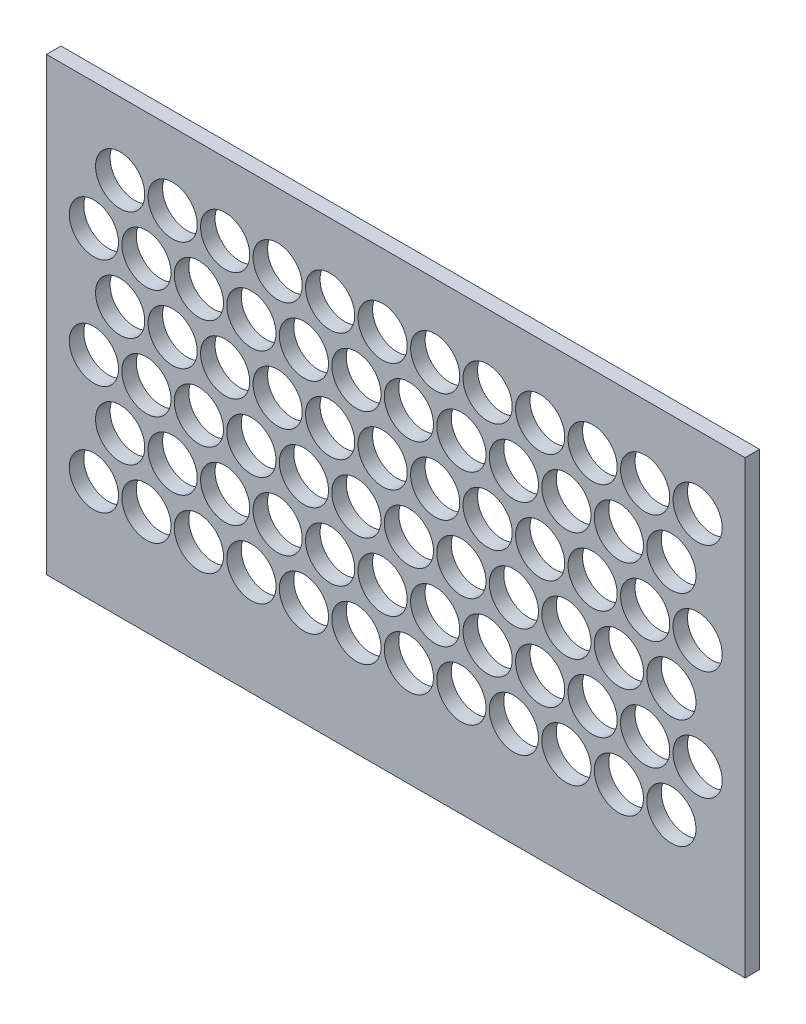
SolidWorks part; units mm, degrees
material "ABS"
ref_plane "X-Y Datum" through (0, 0, 0) normal (0, 0, 1) x (1, 0, 0)
ref_plane "X-Z Datum" through (0, 0, 0) normal (0, 1, 0) x (1, 0, 0)
ref_plane "Y-Z Datum" through (0, 0, 0) normal (1, 0, 0) x (0, 0, -1)
sketch "Sketch1" plane through (0, 0, 0) normal (0, 0, 1) x (1, 0, 0)
  line L1 (-143.025, 70.775) -> (143.025, 70.775)
  line L2 (-143.025, 70.775) -> (-143.025, -70.775)
  line L3 (-143.025, -70.775) -> (143.025, -70.775)
  line L4 (143.025, 70.775) -> (143.025, -70.775)
  line L5 (-143.025, 70.775) -> (143.025, -70.775) construction
  line L6 (-143.025, -70.775) -> (143.025, 70.775) construction
  line L13 (-153.025, -105.775) -> (153.025, -105.775)
  line L14 (-153.025, 91.65) -> (153.025, 91.65)
  line L15 (-153.025, 91.65) -> (-153.025, -105.775)
  line L16 (153.025, 91.65) -> (153.025, -105.775)
  line L17 (153.025, 70.775) -> (153.025, -70.775) construction
  line L18 (-143.025, 91.65) -> (143.025, 91.65) construction
  line L19 (-143.025, -105.775) -> (143.025, -105.775) construction
  line L20 (-153.025, 70.775) -> (-153.025, -70.775) construction
  line L21 (-132.25, -60) -> (-109.25, -60) construction
  circle A0 centre (-132.25, -60) radius 10.775
  circle A1 centre (-109.25, -60) radius 10.775 construction
  circle A2 centre (-120.75, -36) radius 10.775
  point P0 (0, 0)
  point P16 (-120.75, -60)
  dimension "D1" = 21.55
  dimension "D2" = 23
  dimension "D3" = 24
  dimension "D5" = 141.55
  dimension "D6" = 286.05
  dimension "D7" = 35
  dimension "D8" = 20.875
  dimension "D9" = 10
  dimension "D10" = 10
extrude "Boss-Extrude1" add sketch "Sketch1" along normal blind 6.35 contours A0 L3 L4 L1 L2 A2 | A2 | A0 | A0 L2 L3 | L1 L4 L3 L2 region at (2.4105, 0.9241, 0) region at (-140.6182, -68.3682, 0) region at (-132.25, -60, 0) region at (-149.383, -7.0625, 0) region at (-120.75, -36, 0)
sketch "Sketch3" plane through (0, 0, 6.35) normal (0, 0, 1) x (1, 0, 0)
  line L4 (143.025, 70.775) -> (-143.025, 70.775)
  line L5 (143.025, -70.775) -> (143.025, 70.775)
  line L6 (-143.025, -70.775) -> (143.025, -70.775)
  line L7 (-143.025, 70.775) -> (-143.025, -70.775)
  line L8 (143.025, 70.775) -> (-143.025, 70.775)
  line L9 (143.025, -70.775) -> (143.025, 70.775)
  line L10 (-143.025, -70.775) -> (143.025, -70.775)
  line L11 (-143.025, 70.775) -> (-143.025, -70.775)
  circle A1 centre (-120.75, -36) radius 10.775
  circle A2 centre (-120.75, -36) radius 10.775
  circle A3 centre (-132.25, -60) radius 10.775
  circle A4 centre (-132.25, -60) radius 10.775
  dimension "D1" = 0
  dimension "D2" = 0
  dimension "D3" = 0
extrude "Cut-Extrude1" cut sketch "Sketch3" against normal through all contours A4 region at (-132.25, -60, 6.35)
sketch "Sketch4" plane through (0, 0, 6.35) normal (0, 0, 1) x (1, 0, 0)
  line L4 (143.025, 70.775) -> (-143.025, 70.775)
  line L5 (143.025, -70.775) -> (143.025, 70.775)
  line L6 (-143.025, -70.775) -> (143.025, -70.775)
  line L7 (-143.025, 70.775) -> (-143.025, -70.775)
  line L8 (143.025, 70.775) -> (-143.025, 70.775)
  line L9 (143.025, -70.775) -> (143.025, 70.775)
  line L10 (-143.025, -70.775) -> (143.025, -70.775)
  line L11 (-143.025, 70.775) -> (-143.025, -70.775)
  circle A1 centre (-120.75, -36) radius 10.775
  circle A2 centre (-120.75, -36) radius 10.775
  circle A3 centre (-132.25, -60) radius 10.775
  circle A4 centre (-132.25, -60) radius 10.775
  dimension "D1" = 0
  dimension "D2" = 0
  dimension "D3" = 0
extrude "Cut-Extrude2" cut sketch "Sketch4" against normal through all contours A2 region at (-120.75, -36, 6.35)
pattern_linear "LPattern1" count 12 spacing 23 along (1, 0, 0) of "Cut-Extrude1", "Cut-Extrude2"
pattern_linear "LPattern2" count 3 spacing 48 along (0, 1, 0) of "LPattern1"
